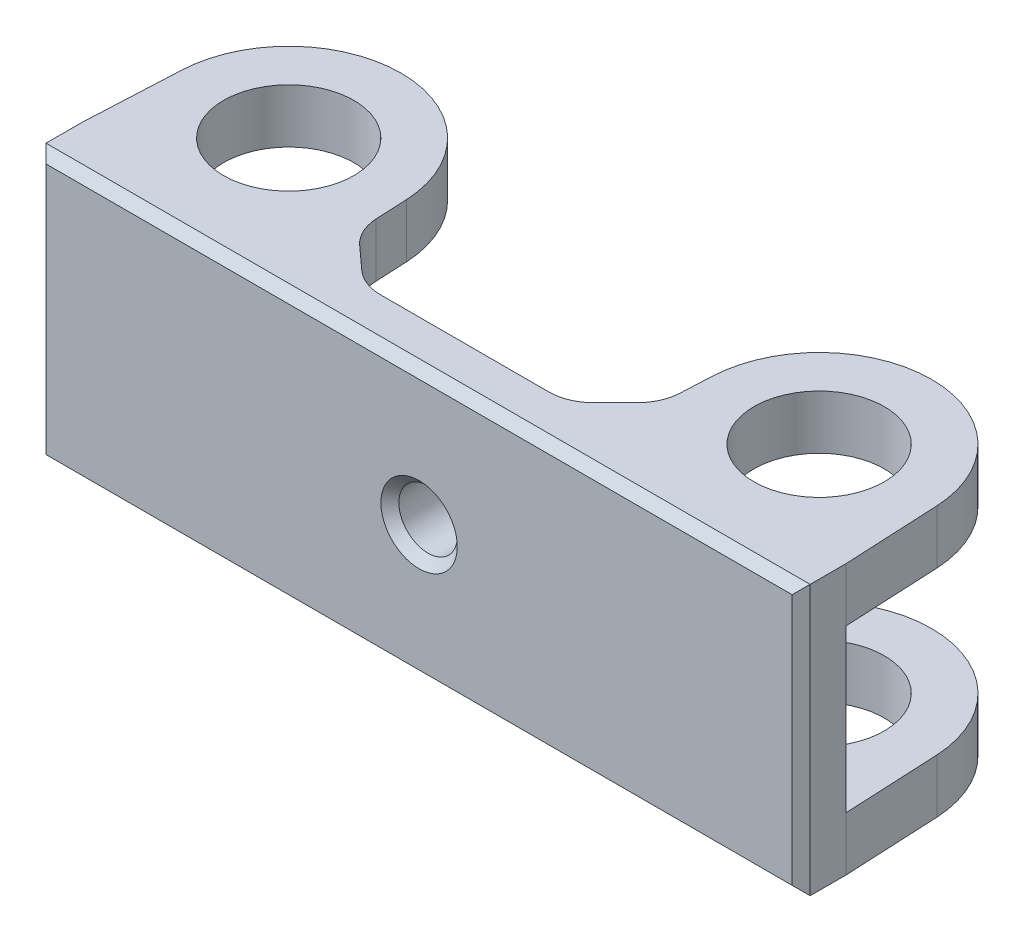
SolidWorks part; units mm, degrees
ref_plane "Front Plane" through (0, 0, 0) normal (0, 0, 1) x (1, 0, 0)
ref_plane "Top Plane" through (0, 0, 0) normal (0, 1, 0) x (1, 0, 0)
ref_plane "Right Plane" through (0, 0, 0) normal (1, 0, 0) x (0, 0, -1)
sketch "Sketch1" plane through (0, 0, 0) normal (0, 0, 1) x (1, 0, 0)
  line L1 (-42.5, -15) -> (42.5, -15)
  line L2 (-42.5, -15) -> (-42.5, 15)
  line L3 (-42.5, 15) -> (42.5, 15)
  line L4 (42.5, -15) -> (42.5, 15)
  line L5 (-42.5, -15) -> (42.5, 15) construction
  line L6 (-42.5, 15) -> (42.5, -15) construction
  circle A0 centre (0, 0) radius 3.25
  point P0 (0, 0)
  dimension "D3" = 6.5
  dimension "D1" = 30
  dimension "D2" = 85
extrude "Boss-Extrude1" add sketch "Sketch1" along normal blind 5
sketch "Sketch3" plane through (0, 15, 0) normal (0, 1, 0) x (1, 0, 0)
  line L0 (42.5, 0) -> (41.9853, 10.6059)
  line L1 (42.5, 0) -> (16.5, 0)
  line L3 (29.5, 10) -> (29.5, -13.5774) construction
  line L4 (16.5, 0) -> (17.0147, 10.6059)
  line L5 (0, 0) -> (0, -15.206) construction
  line L6 (-42.5, 0) -> (-41.9853, 10.6059)
  line L7 (-42.5, 0) -> (-16.5, 0)
  line L8 (-16.5, 0) -> (-17.0147, 10.6059)
  circle A0 centre (29.5, 10) radius 7.25
  circle A1 centre (-29.5, 10) radius 7.25
  arc A2 (41.9853, 10.6059) -> (17.0147, 10.6059) centre (29.5, 10) ccw
  arc A3 (-41.9853, 10.6059) -> (-17.0147, 10.6059) centre (-29.5, 10) cw
  dimension "D1" = 14.5
  dimension "D5" = 25
  dimension "D2" = 59
  dimension "D4" = 10
extrude "Boss-Extrude2" add sketch "Sketch3" against normal blind 6
chamfer "Chamfer2" distance 5 angle 45 2 edges at (-16.5, 12, 0) (16.5, 12, 0) first distance on face at (-16.7573, 12, -5.3029) first distance on face at (0, 4.5, 0)
fillet "Fillet1" radius 5 4 edges at (-16.7424, 12, -4.9941) (-11.2388, 12, 0) (11.5, 12, 0) (16.755, 12, -5.255)
mirror "Mirror1" about plane through (0, 0, 0) normal (0, 1, 0) of "Fillet1", "Boss-Extrude2", "Chamfer2"
sketch "Sketch4" plane through (0, 0, 5) normal (0, 0, 1) x (1, 0, 0)
  line L1 (-18, -12) -> (18, -12)
  line L2 (-18, -12) -> (-18, 12)
  line L3 (-18, 12) -> (18, 12)
  line L4 (18, -12) -> (18, 12)
  line L5 (-18, -12) -> (18, 12) construction
  line L6 (-18, 12) -> (18, -12) construction
  point P0 (0, 0)
  dimension "D1" = 36
  dimension "D2" = 24
sketch "Sketch5" plane through (0, 0, 0) normal (0, 0, -1) x (-1, 0, 0)
  circle A0 centre (0, 0) radius 6.5
  circle A1 centre (0, 0) radius 3.25
  dimension "D1" = 13
  dimension "D2" = 6.5
extrude "Boss-Extrude3" add sketch "Sketch5" along normal blind 5
chamfer "Chamfer1" distance 5 angle 45 1 edges at (-6.5, 0, 0)
chamfer "Chamfer3" distance 1 angle 45 5 edges at (3.25, 0, 5) (0, -15, 5) (-42.5, 0, 5) (0, 15, 5) (42.5, 0, 5)
